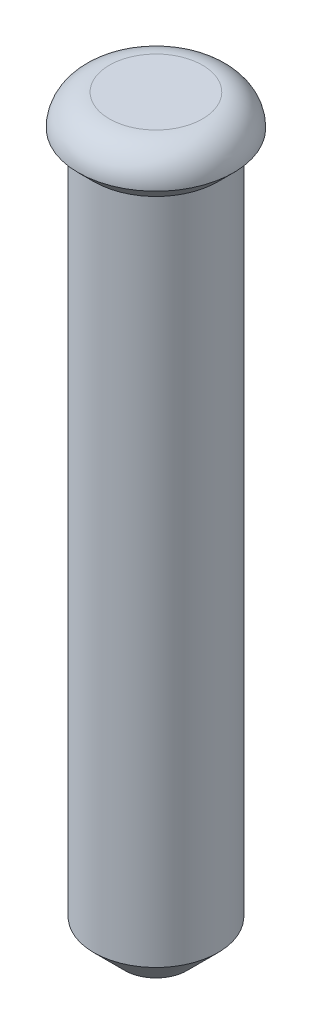
SolidWorks part; units mm, degrees
material "Plain Carbon Steel"
ref_plane "Front Plane" through (0, 0, 0) normal (0, 0, 1) x (1, 0, 0)
ref_plane "Top Plane" through (0, 0, 0) normal (0, 1, 0) x (1, 0, 0)
ref_plane "Right Plane" through (0, 0, 0) normal (1, 0, 0) x (0, 0, -1)
sketch "Sketch1" plane through (0, 0, 0) normal (0, 1, 0) x (1, 0, 0)
  circle A0 centre (0, 0) radius 1
  dimension "D1" = 2
extrude "Boss-Extrude1" add sketch "Sketch1" against normal blind 11
sketch "Sketch2" plane through (0, 0, 0) normal (0, 1, 0) x (1, 0, 0)
  circle A0 centre (0, 0) radius 1.25
  dimension "D1" = 2.5
extrude "Boss-Extrude2" add sketch "Sketch2" along normal blind 1
chamfer "Chamfer1" distance 0.5 angle 45 1 edges at (0, 0, 1.25)
chamfer "Chamfer2" distance 0.5 angle 45 1 edges at (0, -11, 1)
fillet "Fillet1" radius 0.5 1 edges at (0, 1, 1.25)
